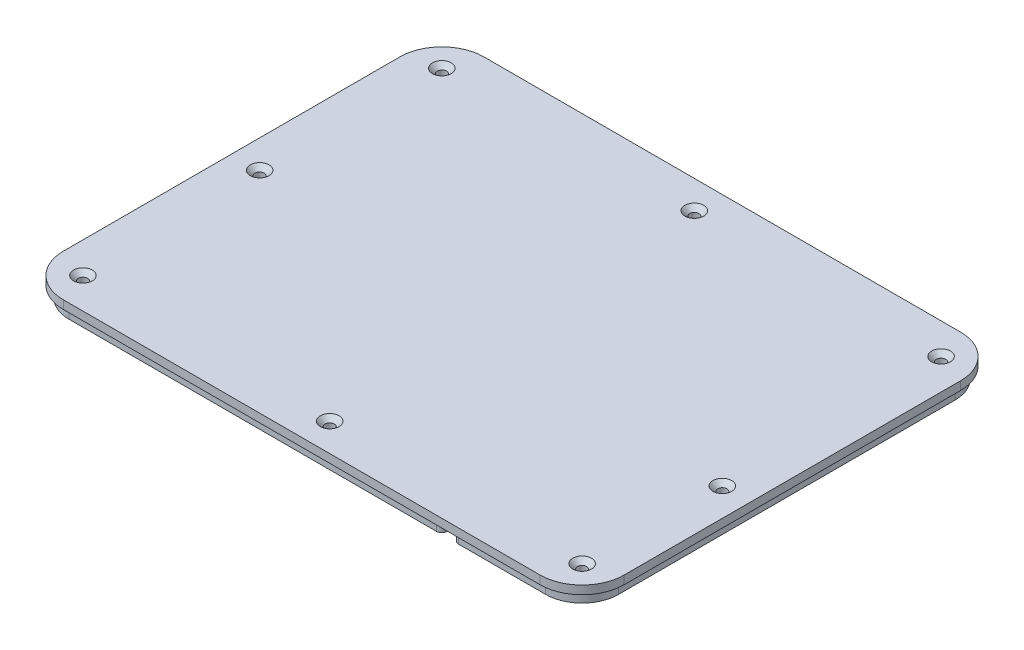
SolidWorks part; units mm, degrees
material "ColorFabb woodFILL"
ref_plane "Front Plane" through (0, 0, 0) normal (0, 0, 1) x (1, 0, 0)
ref_plane "Top Plane" through (0, 0, 0) normal (0, 1, 0) x (1, 0, 0)
ref_plane "Right Plane" through (0, 0, 0) normal (1, 0, 0) x (0, 0, -1)
sketch "BasePlate" plane through (0, 0, 0) normal (0, 1, 0) x (1, 0, 0)
  line L0 (90, -10) -> (94, -10)
  line L1 (-85, 75) -> (85, 75)
  line L2 (-100, 60) -> (-100, -60)
  line L3 (-85, -75) -> (85, -75)
  line L4 (100, 60) -> (100, -60)
  line L5 (88, 60) -> (94, 60)
  line L6 (90, -20) -> (94, -20)
  line L7 (92, 56) -> (62, 56)
  line L8 (-94, 54) -> (-94, 9)
  line L9 (-79, -69) -> (-9, -69)
  line L10 (92, 56) -> (92, 40)
  line L11 (-79, 69) -> (-9, 69)
  line L12 (-94, -9) -> (-94, -54)
  line L13 (9, 69) -> (79, 69)
  line L14 (92, 40) -> (62, 40)
  line L15 (62, 56) -> (62, 40)
  line L16 (9, -69) -> (79, -69)
  line L17 (98, 4) -> (88, 4)
  line L18 (88, -60) -> (94, -60)
  line L19 (88, -59) -> (94, -59)
  line L20 (98, 29) -> (88, 29)
  line L21 (88, 4) -> (88, 29)
  line L22 (98, -54) -> (84, -54)
  line L23 (98, -45) -> (84, -45)
  line L24 (84, -54) -> (84, -45)
  line L25 (98, -27) -> (93, -27)
  line L26 (98, -34.5) -> (93, -34.5)
  line L27 (-85, 73) -> (46, 73)
  line L28 (54, 73) -> (85, 73)
  line L29 (98, 60) -> (98, -60)
  line L30 (54, -73) -> (85, -73)
  line L31 (-85, -73) -> (46, -73)
  line L32 (-98, 60) -> (-98, -60)
  line L33 (93, -27) -> (93, -34.5)
  line L34 (9, -68) -> (79, -68)
  line L35 (-79, -68) -> (-9, -68)
  line L36 (-93, -9) -> (-93, -54)
  line L37 (-93, 54) -> (-93, 9)
  line L38 (-79, 68) -> (-9, 68)
  line L39 (9, 68) -> (79, 68)
  line L40 (88, 59) -> (94, 59)
  line L41 (90, -9) -> (94, -9)
  line L42 (90, -21) -> (94, -21)
  line L43 (97, -56) -> (97, -24)
  line L44 (97, 56) -> (97, -6)
  arc A0 (85, 75) -> (100, 60) centre (85, 60) cw
  arc A1 (85, -75) -> (100, -60) centre (85, -60) ccw
  arc A2 (-100, -60) -> (-85, -75) centre (-85, -60) ccw
  arc A3 (-85, 75) -> (-100, 60) centre (-85, 60) ccw
  arc A4 (94, 60) -> (98, 56) centre (94, 56) cw
  arc A5 (94, -10) -> (98, -6) centre (94, -6) ccw
  arc A6 (48, 71) -> (52, 71) centre (50, 71) ccw
  arc A7 (48, 71) -> (46, 73) centre (46, 71) ccw
  circle A8 centre (55, 0) radius 5
  circle A9 centre (55, 0) radius 25
  circle A10 centre (-55, 0) radius 15
  circle A11 centre (55, 0) radius 22
  arc A12 (-90, -5) -> (-90, 5) centre (-90, 0) ccw
  arc A13 (-90, 5) -> (-94, 9) centre (-90, 9) cw
  arc A14 (-90, -5) -> (-94, -9) centre (-90, -9) ccw
  arc A15 (5, 65) -> (-5, 65) centre (0, 65) cw
  arc A16 (-5, 65) -> (-9, 69) centre (-9, 65) ccw
  arc A17 (5, 65) -> (9, 69) centre (9, 65) cw
  arc A18 (-5, -65) -> (5, -65) centre (0, -65) cw
  arc A19 (-5, -65) -> (-9, -69) centre (-9, -65) cw
  arc A20 (5, -65) -> (9, -69) centre (9, -65) ccw
  arc A21 (52, 71) -> (54, 73) centre (54, 71) cw
  arc A22 (94, -20) -> (98, -24) centre (94, -24) cw
  circle A23 centre (90, -15) radius 1.65
  arc A24 (85, 63) -> (88, 60) centre (88, 63) ccw
  arc A25 (85, 63) -> (79, 69) centre (79, 63) ccw
  arc A26 (52, -71) -> (48, -71) centre (50, -71) ccw
  circle A27 centre (-89, 64) radius 1.65
  arc A28 (-85, 63) -> (-88, 60) centre (-88, 63) cw
  arc A29 (-88, 60) -> (-94, 54) centre (-88, 54) ccw
  arc A30 (-85, 63) -> (-79, 69) centre (-79, 63) cw
  circle A31 centre (89, 64) radius 1.65
  arc A32 (85, -63) -> (79, -69) centre (79, -63) cw
  arc A33 (85, -63) -> (88, -60) centre (88, -63) cw
  arc A34 (94, -60) -> (98, -56) centre (94, -56) ccw
  circle A35 centre (89, -64) radius 1.65
  arc A36 (-88, -60) -> (-85, -63) centre (-88, -63) cw
  arc A37 (-85, -63) -> (-79, -69) centre (-79, -63) ccw
  arc A38 (-88, -60) -> (-94, -54) centre (-88, -54) cw
  circle A39 centre (-89, -64) radius 1.65
  circle A40 centre (0, 65) radius 1.65
  circle A41 centre (-90, 0) radius 1.65
  circle A42 centre (0, -65) radius 1.65
  arc A43 (90, -10) -> (90, -20) centre (90, -15) ccw
  arc A44 (48, -71) -> (46, -73) centre (46, -71) cw
  arc A45 (52, -71) -> (54, -73) centre (54, -71) ccw
  circle A46 centre (79, 63) radius 3
  circle A47 centre (79, 63) radius 1.25
  circle A48 centre (92, 34) radius 3
  circle A49 centre (92, 34) radius 1.25
  circle A50 centre (92, -1) radius 3
  circle A51 centre (92, -1) radius 1.25
  circle A52 centre (80, -20) radius 3
  circle A53 centre (80, -20) radius 1.25
  circle A54 centre (79, -63) radius 3
  circle A55 centre (79, -63) radius 1.25
  circle A56 centre (11, -63) radius 3
  circle A57 centre (11, -63) radius 1.25
  circle A58 centre (-11, -63) radius 3
  circle A59 centre (-11, -63) radius 1.25
  arc A60 (94, -59) -> (97, -56) centre (94, -56) ccw
  arc A61 (84, -63) -> (88, -59) centre (88, -63) cw
  arc A62 (84, -63) -> (79, -68) centre (79, -63) cw
  arc A63 (6, -65) -> (9, -68) centre (9, -65) ccw
  circle A64 centre (-11, 63) radius 3
  circle A65 centre (-11, 63) radius 1.25
  circle A66 centre (11, 63) radius 3
  circle A67 centre (11, 63) radius 1.25
  circle A68 centre (-70, 20) radius 3
  circle A69 centre (-40, 20) radius 3
  circle A70 centre (-40, 20) radius 1.25
  circle A71 centre (-70, 20) radius 1.25
  circle A72 centre (-70, -20) radius 3
  circle A73 centre (-70, -20) radius 1.25
  circle A74 centre (-40, -20) radius 3
  circle A75 centre (-40, -20) radius 1.25
  circle A76 centre (20, 20) radius 3
  arc A77 (85, 73) -> (98, 60) centre (85, 60) cw
  arc A78 (85, -73) -> (98, -60) centre (85, -60) ccw
  circle A79 centre (20, -20) radius 3
  circle A80 centre (20, -20) radius 1.25
  circle A81 centre (20, 20) radius 1.25
  arc A82 (-98, -60) -> (-85, -73) centre (-85, -60) ccw
  arc A83 (-85, 73) -> (-98, 60) centre (-85, 60) ccw
  arc A84 (-6, -65) -> (6, -65) centre (0, -65) cw
  arc A85 (-6, -65) -> (-9, -68) centre (-9, -65) cw
  arc A86 (-84, -63) -> (-79, -68) centre (-79, -63) ccw
  arc A87 (-88, -59) -> (-84, -63) centre (-88, -63) cw
  arc A88 (-88, -59) -> (-93, -54) centre (-88, -54) cw
  arc A89 (-90, -6) -> (-93, -9) centre (-90, -9) ccw
  arc A90 (-90, -6) -> (-90, 6) centre (-90, 0) ccw
  arc A91 (-90, 6) -> (-93, 9) centre (-90, 9) cw
  arc A92 (-88, 59) -> (-93, 54) centre (-88, 54) ccw
  arc A93 (-84, 63) -> (-88, 59) centre (-88, 63) cw
  arc A94 (-84, 63) -> (-79, 68) centre (-79, 63) cw
  arc A95 (-6, 65) -> (-9, 68) centre (-9, 65) ccw
  arc A96 (6, 65) -> (-6, 65) centre (0, 65) cw
  arc A97 (6, 65) -> (9, 68) centre (9, 65) cw
  arc A98 (84, 63) -> (79, 68) centre (79, 63) ccw
  arc A99 (84, 63) -> (88, 59) centre (88, 63) ccw
  arc A100 (94, 59) -> (97, 56) centre (94, 56) cw
  arc A101 (94, -9) -> (97, -6) centre (94, -6) ccw
  arc A102 (90, -9) -> (90, -21) centre (90, -15) ccw
  arc A103 (94, -21) -> (97, -24) centre (94, -24) cw
  circle A104 centre (-55, 0) radius 35 construction
  circle A105 centre (-55, 0) radius 27.5
  circle A106 centre (-55, 0) radius 22.5
extrude "Base Plate" add sketch "BasePlate" against normal blind 3 contours L2 A2 L3 A1 L4 A0 L1 A3
extrude "Inner Base Profile" add sketch "BasePlate<4>" against normal blind 4 from surface contours A83 L32 A82 L31 A44 A26 A45 L30 A78 L29 A77 L28 A21 A6 A7 L27 starting at face at (0, -3, 0)
sketch "BasePlate<4>" plane through (0, 0, 0) normal (0, 1, 0) x (1, 0, 0) same geometry as "BasePlate"
extrude "Mounting Holes" cut sketch "BasePlate<5>" along normal up to surface (-7 mm away) contours A39 | A41 | A27 | A42 | A35 | A23 | A31 | A40 up to face at (25, -7, 0)
sketch "BasePlate<5>" plane through (0, 0, 0) normal (0, 1, 0) x (1, 0, 0) same geometry as "BasePlate"
chamfer "Countersink" distance 1.7 angle 45 8 edges at (-89, 0, 65.65) (89, 0, -62.35) (90, 0, 16.65) (89, 0, 65.65) (0, 0, 66.65) (0, 0, -63.35) (-89, 0, -62.35) (-90, 0, 1.65)
